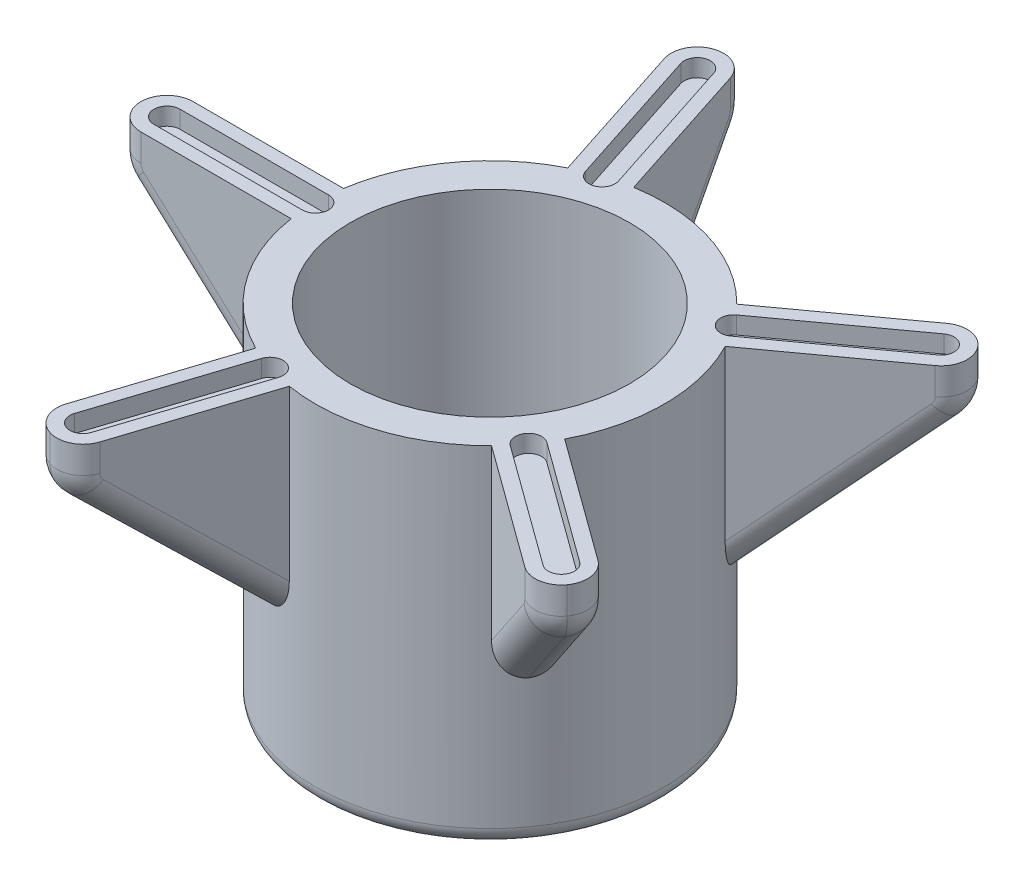
SolidWorks part; units mm, degrees
ref_plane "前视基准面" through (0, 0, 0) normal (0, 0, 1) x (1, 0, 0)
ref_plane "上视基准面" through (0, 0, 0) normal (0, 1, 0) x (1, 0, 0)
ref_plane "右视基准面" through (0, 0, 0) normal (1, 0, 0) x (0, 0, -1)
other "Configuration Table"
sketch "草图1" plane through (0, 0, 0) normal (0, 1, 0) x (1, 0, 0)
  circle A0 centre (0, 0) radius 50
  circle A1 centre (0, 0) radius 40
  dimension "D1" = 100
  dimension "D2" = 10
extrude "凸台-拉伸1" add sketch "草图1" along normal blind 100
sketch "草图2" plane through (0, 0, 0) normal (0, 0, 1) x (1, 0, 0)
  line L0 (-50, 100) -> (-100, 100)
  line L2 (50, 100) -> (-50, 100) construction
  line L3 (-100, 100) -> (-100, 92.2241)
  line L4 (-96.7565, 84.8519) -> (-50, 42)
  line L5 (-50, 100) -> (-47.086, 100)
  line L6 (-47.086, 100) -> (-47.086, 42)
  line L7 (-47.086, 42) -> (-50, 42)
  arc A0 (-96.7565, 84.8519) -> (-100, 92.2241) centre (-90, 92.2241) cw
  dimension "D4" = 10
  dimension "D1" = 100
  dimension "D2" = 50
  dimension "D3" = 58
extrude "凸台-拉伸2" add sketch "草图2" against normal mid plane 15
fillet "圆角1" radius 7.5 6 edges at (-100, 96.112, -7.5) (-99.1533, 88.197, -7.5) (-100, 96.112, 7.5) (-99.1533, 88.197, 7.5) (-73.3783, 63.4259, -7.5) (-73.3783, 63.4259, 7.5)
sketch "草图3" plane through (0, 100, 0) normal (0, 1, 0) x (1, 0, 0)
  line L0 (-92.5, 0) -> (-50, 0) construction
  line L1 (-92.5, 3.75) -> (-50, 3.75)
  line L2 (-92.5, -3.75) -> (-50, -3.75)
  arc A0 (-92.5, 3.75) -> (-92.5, -3.75) centre (-92.5, 0) ccw
  arc A1 (-50, -3.75) -> (-50, 3.75) centre (-50, 0) ccw
  point P3 (-71.25, 0)
  point P8 (0, 0)
  dimension "D1" = 7.5
  dimension "D2" = 92.5
  dimension "D3" = 50
extrude "切除-拉伸1" cut sketch "草图3" against normal blind 5
ref_axis "基准轴1" through (0, 105, 0) along (0, -1, 0)
pattern_circular "阵列(圆周)1" count 5 every 72 about axis through (0, 105, 0) along (0, -1, 0) of "切除-拉伸1", "圆角1", "凸台-拉伸2"
fillet "圆角2" radius 5 1 edges at (0, 0, 50)
ref_plane "基准面2" through (3.1624, 3.4506, 0) normal (0.6757, 0.7372, 0) x (0.7372, -0.6757, 0)
sketch "草图3<3>" plane through (0, 100, 0) normal (0, 1, 0) x (1, 0, 0) same geometry as "草图3"
